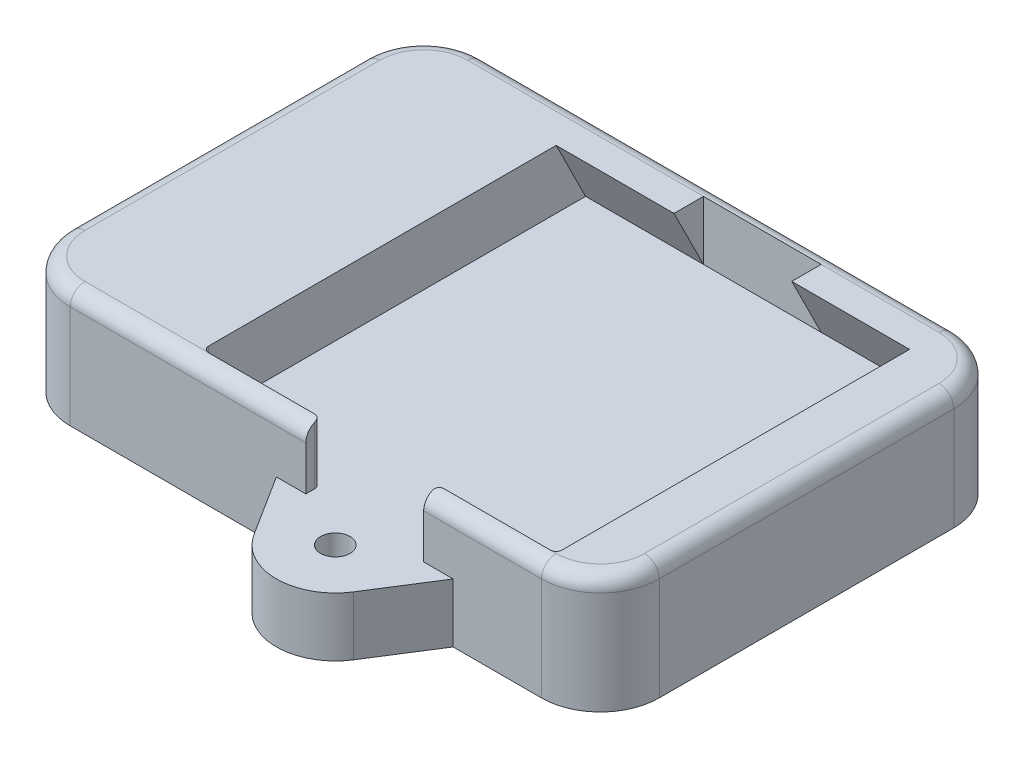
SolidWorks part; units mm, degrees
ref_plane "Front Plane" through (0, 0, 0) normal (0, 0, 1) x (1, 0, 0)
ref_plane "Top Plane" through (0, 0, 0) normal (0, 1, 0) x (1, 0, 0)
ref_plane "Right Plane" through (0, 0, 0) normal (1, 0, 0) x (0, 0, -1)
sketch "Sketch1" plane through (0, 0, 0) normal (0, 1, 0) x (1, 0, 0)
  line L1 (40, -35) -> (-40, -35)
  line L2 (50, -25) -> (50, 25)
  line L3 (40, 35) -> (-40, 35)
  line L4 (-50, -25) -> (-50, 25)
  line L5 (50, -35) -> (-50, 35) construction
  line L6 (50, 35) -> (-50, -35) construction
  arc A0 (-40, 35) -> (-50, 25) centre (-40, 25) ccw
  arc A1 (50, 25) -> (40, 35) centre (40, 25) ccw
  arc A2 (40, -35) -> (50, -25) centre (40, -25) ccw
  arc A3 (-40, -35) -> (-50, -25) centre (-40, -25) cw
  point P0 (0, 0)
  dimension "D3" = 10
  dimension "D1" = 100
  dimension "D2" = 70
extrude "Boss-Extrude1" add sketch "Sketch1" along normal blind 20
fillet "Fillet1" radius 2.5 8 edges at (-47.0711, 20, -32.0711) (0, 20, -35) (47.0711, 20, -32.0711) (50, 20, 0) (47.0711, 20, 32.0711) (0, 20, 35) (-47.0711, 20, 32.0711) (-50, 20, 0)
sketch "Sketch3" plane through (0, 0, 0) normal (0, -1, 0) x (1, 0, 0)
  line L0 (-50, -25) -> (-50, 25) construction
  line L1 (-50, 1.25) -> (-30, 1.25)
  line L2 (-50, 1.25) -> (-50, 6.875)
  line L3 (-50, 6.875) -> (-30, 6.875)
  line L4 (-30, 1.25) -> (-30, 6.875)
  line L5 (-50, 1.25) -> (-30, 6.875) construction
  line L6 (-50, 6.875) -> (-30, 1.25) construction
  line L7 (-50, 9.38) -> (-30, 9.38)
  line L8 (-50, 9.38) -> (-50, 15.005)
  line L9 (-50, 15.005) -> (-30, 15.005)
  line L10 (-30, 9.38) -> (-30, 15.005)
  line L11 (-50, 9.38) -> (-30, 15.005) construction
  line L12 (-50, 15.005) -> (-30, 9.38) construction
  line L13 (-50, -14.995) -> (-30, -14.995)
  line L14 (-50, -14.995) -> (-50, -9.37)
  line L15 (-50, -9.37) -> (-30, -9.37)
  line L16 (-30, -14.995) -> (-30, -9.37)
  line L17 (-50, -6.87) -> (-30, -6.87)
  line L18 (-50, -6.87) -> (-50, -1.25)
  line L19 (-50, -1.25) -> (-30, -1.25)
  line L20 (-30, -6.87) -> (-30, -1.25)
  line L21 (-50, -14.995) -> (-30, -9.37) construction
  line L22 (-50, -9.37) -> (-30, -14.995) construction
  line L23 (-50, -6.87) -> (-30, -1.25) construction
  line L24 (-50, -1.25) -> (-30, -6.87) construction
  point P0 (-40, 4.0625)
  point P5 (-40, 12.1925)
  point P16 (-40, -12.1975)
  point P21 (-40, -4.0675)
  dimension "D1" = 5.625
  dimension "D2" = 20
  dimension "D3" = 1.25
  dimension "D6" = 2.5
  dimension "D5" = 2.5
  dimension "D7" = 5.62
  dimension "D8" = 5.625
  dimension "D4" = 2
extrude "Boss-Extrude2" add sketch "Sketch3" along normal blind 16
fillet "Fillet2" radius 10 8 edges at (-30, -16, -12.1825) (-30, -16, -4.06) (-30, -16, 4.0625) (-30, -16, 12.1925) (-50, -16, -12.1825) (-50, -16, -4.06) (-50, -16, 4.0625) (-50, -16, 12.1925)
sketch "Sketch4" plane through (0, 0, 15.005) normal (0, 0, 1) x (1, 0, 0)
  circle A0 centre (-40, -8.5) radius 2.5
  dimension "D1" = 5
  dimension "D2" = 7.5
extrude "Cut-Extrude1" cut sketch "Sketch4" against normal through all
sketch "Sketch5" plane through (0, 0, 0) normal (0, -1, 0) x (1, 0, 0)
  line L0 (-40, 6.875) -> (-40, 1.25) construction
  line L1 (-40, 1.25) -> (0, 1.25)
  line L2 (-40, 1.25) -> (-40, 6.87)
  line L3 (-40, 6.87) -> (0, 6.87)
  line L4 (0, 1.25) -> (0, 6.87)
  line L5 (-40, 1.25) -> (0, 6.87) construction
  line L6 (-40, 6.87) -> (0, 1.25) construction
  line L7 (-40, -6.87) -> (0, -6.87)
  line L8 (-40, -6.87) -> (-40, -1.25)
  line L9 (-40, -1.25) -> (0, -1.25)
  line L10 (0, -6.87) -> (0, -1.25)
  line L11 (-40, -6.87) -> (0, -1.25) construction
  line L12 (-40, -1.25) -> (0, -6.87) construction
  point P0 (-20, 4.06)
  point P8 (-20, -4.06)
  dimension "D1" = 40
  dimension "D2" = 20
  dimension "D4" = 5.62
  dimension "D5" = 2.5
  dimension "D6" = 1.25
  dimension "D3" = 2
extrude "Boss-Extrude3" add sketch "Sketch5" along normal blind 15
chamfer "Chamfer1" distance 15 angle 67 2 edges at (0, -15, -4.06) (0, -15, 4.06) first distance on face at (0, -7.5, -4.06) first distance on face at (0, -7.5, 4.06)
sketch "Sketch6" plane through (0, 0, 15.005) normal (0, 0, 1) x (1, 0, 0)
  circle A0 centre (-40, -8.5) radius 2.5 construction
  circle A1 centre (-40, -8.5) radius 2.5
extrude "Cut-Extrude2" cut sketch "Sketch6" against normal through all
sketch "Sketch7" plane through (0, 20, 0) normal (0, 1, 0) x (1, 0, 0)
  line L0 (0, -33.5) -> (0, -42.5)
  line L1 (-19, -32.5) -> (-1, -32.5)
  line L2 (-20, -31.5) -> (-20, 32.5)
  line L3 (-20, 32.5) -> (40, 32.5)
  line L4 (40, -31.5) -> (40, 32.5)
  line L5 (-20, -32.5) -> (40, 32.5) construction
  line L6 (-20, 32.5) -> (40, -32.5) construction
  line L7 (0, -42.5) -> (20, -42.5)
  line L8 (20, -42.5) -> (20, -33.5)
  line L9 (21, -32.5) -> (39, -32.5)
  arc A0 (20, -33.5) -> (21, -32.5) centre (21, -33.5) cw
  arc A1 (0, -33.5) -> (-1, -32.5) centre (-1, -33.5) ccw
  arc A2 (39, -32.5) -> (40, -31.5) centre (39, -31.5) ccw
  arc A3 (-19, -32.5) -> (-20, -31.5) centre (-19, -31.5) cw
  point P0 (10, 0)
  point P9 (10, -42.5)
  point P14 (20, -32.5)
  point P17 (0, -32.5)
  dimension "D7" = 1
  dimension "D1" = 60
  dimension "D2" = 65
  dimension "D3" = 10
  dimension "D4" = 0
  dimension "D5" = 20
  dimension "D6" = 10
extrude "Cut-Extrude3" cut sketch "Sketch7" against normal blind 10
sketch "Sketch8" plane through (-20, 0, 0) normal (1, 0, 0) x (0, 0, -1)
  line L0 (32.5, 10) -> (27.5, 20)
  line L1 (32.5, 20) -> (-31.5, 20) construction
  line L2 (27.5, 20) -> (32.5, 20)
  line L3 (32.5, 20) -> (32.5, 10)
  line L4 (32.5, 10) -> (32.5, 20) construction
  dimension "D1" = 5
extrude "Boss-Extrude4" add sketch "Sketch8" along normal blind 20
sketch "Sketch9" plane through (40, 0, 0) normal (-1, 0, 0) x (0, 0, 1)
  line L3 (-32.5, 10) -> (-27.5, 20)
  line L4 (-27.5, 20) -> (-32.5, 20)
  line L5 (-32.5, 20) -> (-32.5, 10)
  line L6 (-32.5, 10) -> (-27.5, 20)
  line L7 (-27.5, 20) -> (-32.5, 20)
  line L8 (-32.5, 20) -> (-32.5, 10)
  dimension "D1" = 0
extrude "Boss-Extrude5" add sketch "Sketch9" along normal blind 20
sketch "Sketch10" plane through (0, 0, 0) normal (0, -1, 0) x (1, 0, 0)
  line L0 (-5, 35) -> (25, 35)
  line L1 (0, 35) -> (-40, 35) construction
  line L2 (40, 35) -> (20, 35) construction
  line L3 (10, -32.5) -> (10, 35) construction
  line L4 (20, -32.5) -> (0, -32.5) construction
  line L6 (1.5505, 45.3485) -> (-5, 35)
  line L7 (18.4495, 45.3485) -> (25, 35)
  arc A0 (18.4495, 45.3485) -> (1.5505, 45.3485) centre (10, 40) ccw
  point P10 (10, 35)
  dimension "D2" = 20
  dimension "D1" = 30
  dimension "D3" = 5
extrude "Boss-Extrude6" add sketch "Sketch10" against normal up to surface (10 mm away) up to face at (10, 10, 14.2857)
sketch "Sketch12" plane through (0, 10, 0) normal (0, 1, 0) x (1, 0, 0)
  circle A0 centre (10, -40) radius 2.5
  dimension "D1" = 5
extrude "Cut-Extrude5" cut sketch "Sketch12" against normal blind 15
